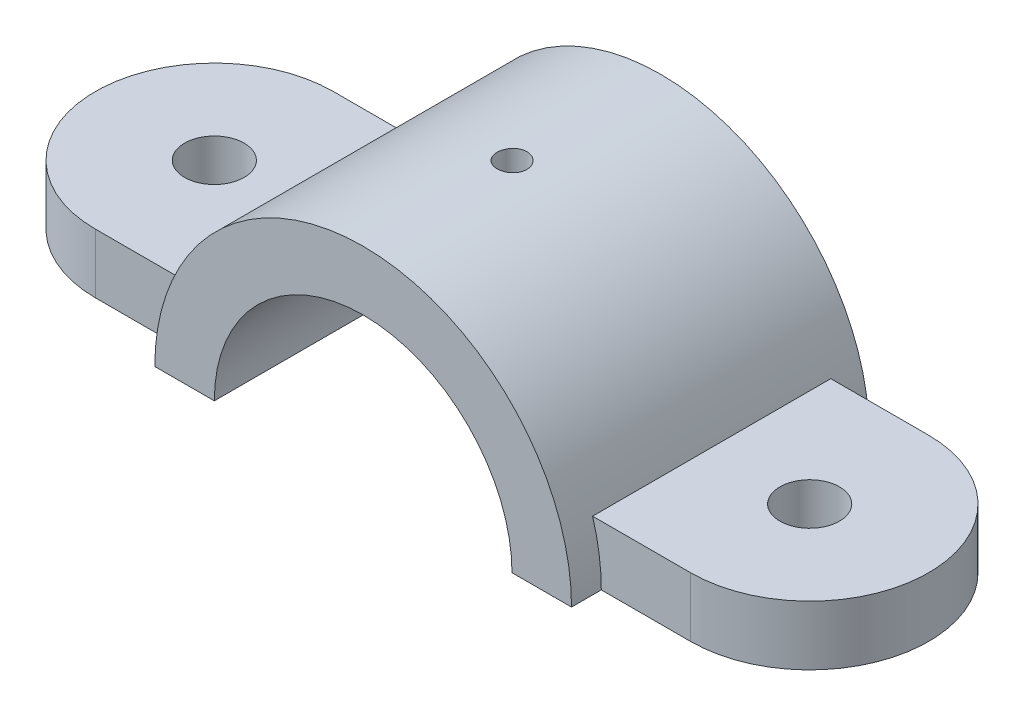
SolidWorks part; units mm, degrees
ref_plane "Front Plane" through (0, 0, 0) normal (0, 0, 1) x (1, 0, 0)
ref_plane "Top Plane" through (0, 0, 0) normal (0, 1, 0) x (1, 0, 0)
ref_plane "Right Plane" through (0, 0, 0) normal (1, 0, 0) x (0, 0, -1)
sketch "slotSketch" plane through (0, 0, 0) normal (0, 1, 0) x (1, 0, 0)
  line L0 (-63.5, 0) -> (63.5, 0) construction
  line L1 (-63.5, 25.4) -> (63.5, 25.4)
  line L2 (-63.5, -25.4) -> (63.5, -25.4)
  line L3 (0, 0) -> (0, 43.3751) construction
  arc A0 (-63.5, 25.4) -> (-63.5, -25.4) centre (-63.5, 0) ccw
  arc A1 (63.5, -25.4) -> (63.5, 25.4) centre (63.5, 0) ccw
  circle A2 centre (63.5, 0) radius 6.35
  circle A3 centre (-63.5, 0) radius 6.35
  point P3 (0, 0)
  dimension "D2" = 25.4
  dimension "D3" = 12.7
  dimension "D1" = 127
extrude "slotExtrude" add sketch "slotSketch" along normal blind 12.7
sketch "Sketch3" plane through (0, 0, 0) normal (0, 0, 1) x (1, 0, 0)
  line L0 (-63.5, 0) -> (63.5, 0) construction
  line L5 (-63.5, 0) -> (63.5, 0)
  line L6 (63.5, 0) -> (63.5, 12.7)
  line L7 (63.5, 12.7) -> (-63.5, 12.7)
  line L8 (-63.5, 12.7) -> (-63.5, 0)
  line L9 (-44.45, 0) -> (44.45, 0)
  arc A0 (-44.45, 0) -> (44.45, 0) centre (0, 0) cw
  dimension "D1" = 44.45
  dimension "D2" = 0
extrude "arcExtrude" add sketch "Sketch3" along normal mid plane 63.5
sketch "Sketch4" plane through (0, 0, 31.75) normal (0, 0, 1) x (1, 0, 0)
  line L0 (-44.45, 0) -> (44.45, 0) construction
  line L1 (-25.4, 19.05) -> (25.4, 19.05)
  line L2 (-25.4, 19.05) -> (-25.4, 0)
  line L3 (-25.4, 0) -> (25.4, 0)
  line L4 (25.4, 19.05) -> (25.4, 0)
  point P6 (0, 0)
  point P7 (0, 0)
  point P9 (0, 0)
  dimension "D1" = 19.05
  dimension "D2" = 50.8
extrude "squareProfile" [suppressed] cut sketch "Sketch4" against normal through all
hole_wizard "centerDrill" positions "Sketch5" profile "Sketch6" hole size "#97" standard "ANSI Inch" end condition through all
sketch "Sketch5" plane through (0, 0, 0) normal (0, -1, 0) x (-1, 0, 0)
  point P0 (0, 0)
sketch "Sketch6" plane through (0, 0, 0) normal (1, 0, 0) x (0, 0, -1)
  line L0 (0, 0) -> (0, 44.45)
  line L1 (0, 44.45) -> (3.175, 44.45)
  line L2 (3.175, 44.45) -> (3.175, 0)
  line L5 (3.175, 0) -> (0, 0)
  line L11 (0, -6.35) -> (0, 107.95) construction
  dimension "Thru Hole Dia." = 6.35
  dimension "Thru Hole Depth" = 44.45
sketch "Sketch7" plane through (0, 0, 31.75) normal (0, 0, 1) x (1, 0, 0)
  line L0 (-44.45, 0) -> (44.45, 0) construction
  line L1 (-31.75, 0) -> (31.75, 0)
  arc A0 (-31.75, 0) -> (31.75, 0) centre (0, 0) cw
  dimension "D1" = 63.5
extrude "arcProfile" cut sketch "Sketch7" against normal through all
equation "\"slotLength\"= 5"
equation "\"slotHole\"= .5"
equation "\"slotRad\"= 1"
equation "\"slotHeight\"= .5"
equation "\"D1@slotSketch\"= \"slotLength\""
equation "\"D2@slotSketch\"= \"slotRad\""
equation "\"D1@slotExtrude\"= \"slotHeight\""
equation "\"D3@slotSketch\"= \"slotHole\""
equation "\"arcRad\"= 1.75"
equation "\"arcExtrude\"= 2.5"
equation "\"D1@Sketch3\"=\"arcRad\""
equation "\"D1@arcExtrude\" = \"arcExtrude\""
